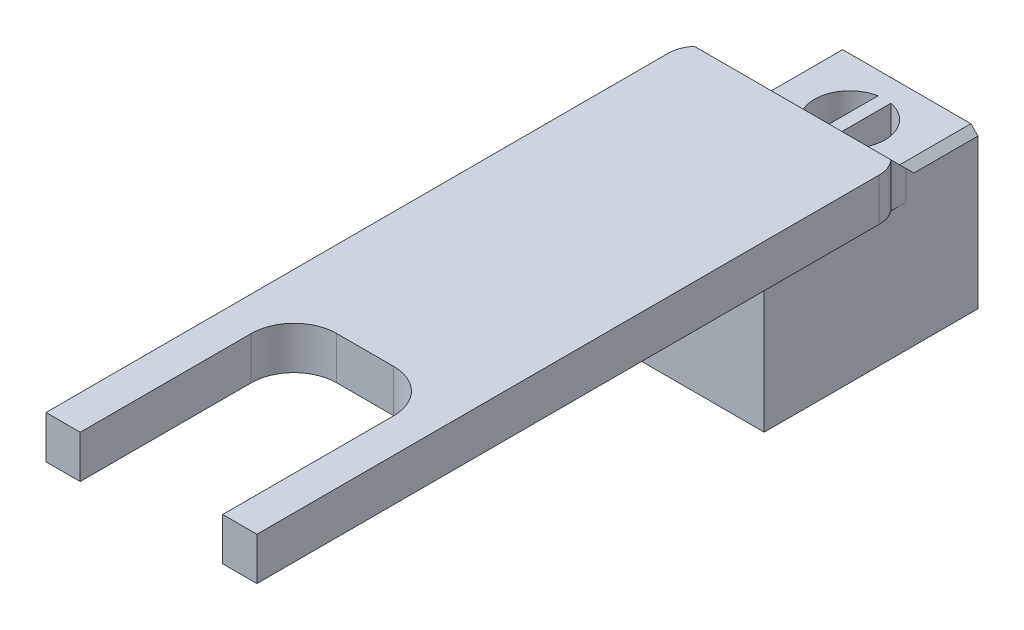
SolidWorks part; units mm, degrees
ref_plane "Front Plane" through (0, 0, 0) normal (0, 0, 1) x (1, 0, 0)
ref_plane "Top Plane" through (0, 0, 0) normal (0, 1, 0) x (1, 0, 0)
ref_plane "Right Plane" through (0, 0, 0) normal (1, 0, 0) x (0, 0, -1)
sketch "Sketch1" plane through (0, 0, 0) normal (0, 1, 0) x (1, 0, 0)
  line L1 (0, 0) -> (12.7, 0)
  line L2 (0, 0) -> (0, -19.05)
  line L3 (0, -19.05) -> (12.7, -19.05)
  line L4 (12.7, 0) -> (12.7, -19.05)
  line L6 (5.7785, -1.22) -> (6.9215, -1.22)
  line L7 (5.7785, -1.22) -> (5.7785, -9.573)
  line L8 (5.7785, -9.573) -> (6.9215, -9.573)
  line L9 (6.9215, -1.22) -> (6.9215, -9.573)
  circle A3 centre (6.35, -5.08) radius 3.1433
  dimension "D5" = 6.35
  dimension "D3" = 5.08
  dimension "D4" = 6.2865
  dimension "D1" = 12.7
  dimension "D2" = 19.05
  dimension "D6" = 0.5715
  dimension "D7" = 0.5715
extrude "Boss-Extrude1" add sketch "Sketch1" along normal blind 13.97 contours L4 L1 L2 L3 | L7 L6 L9 L8 region at (6.35, 0, 10.2234)
sketch "Sketch2" plane through (0, 13.97, 0) normal (0, 1, 0) x (1, 0, 0)
  line L7 (0, -19.05) -> (12.7, -19.05) construction
  line L12 (-3.048, -10.16) -> (15.748, -10.16)
  line L13 (-3.048, -10.16) -> (-3.048, -67.31)
  line L14 (-3.048, -67.31) -> (15.748, -67.31)
  line L15 (15.748, -10.16) -> (15.748, -67.31)
  line L17 (0, 0) -> (0, -19.05) construction
  line L18 (12.7, 0) -> (12.7, -19.05) construction
  line L20 (0, -67.31) -> (12.7, -67.31)
  line L21 (0, -67.31) -> (0, -48.26)
  line L22 (0, -48.26) -> (12.7, -48.26)
  line L23 (12.7, -67.31) -> (12.7, -48.26)
  line M17 (12.7, -19.05) -> (12.7, 0)
  line M19 (0, 0) -> (0, -19.05)
  line M20 (0, -19.05) -> (12.7, -19.05)
  dimension "D1" = 8.89
  dimension "D2" = 48.26
  dimension "D3" = 3.048
  dimension "D4" = 3.048
  dimension "D5" = 3.048
  dimension "D6" = 3.048
  dimension "D7" = 19.05
extrude "Boss-Extrude2" add sketch "Sketch2" along normal blind 3.81 contours L23 L14 L15 L12 L13 L21 L22 M17 M20 M19 | L12 M19 M20 M17 region at (6.35, 13.97, 36.1153) region at (6.35, 13.97, 14.605)
chamfer "Chamfer3" distance 3.81 angle 45 1 edges at (6.35, 13.97, 10.16)
chamfer "Chamfer5" distance 2.54 angle 45 3 edges at (0, 13.97, 14.605) (6.35, 13.97, 19.05) (12.7, 13.97, 14.605)
fillet "Fillet1" radius 3.81 2 edges at (12.7, 15.875, 48.26) (0, 15.875, 48.26)
fillet "Fillet2" radius 3.81 2 edges at (0, 14.605, 10.16) (12.7, 14.605, 10.16)
fillet "Fillet3" radius 2.54 2 edges at (-3.048, 15.875, 10.16) (15.748, 15.875, 10.16)
chamfer "Chamfer6" distance 0.635 angle 45 2 edges at (0, 13.97, 3.175) (12.7, 13.97, 3.175)
